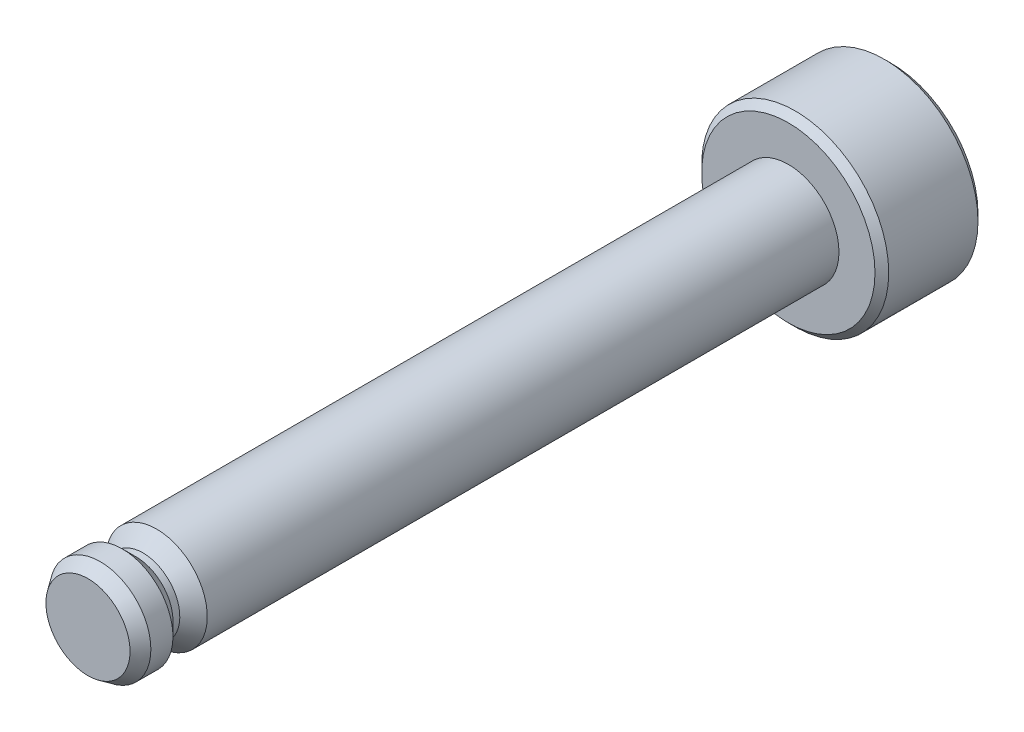
SolidWorks part; units mm, degrees
ref_plane "Front" through (0, 0, 0) normal (0, 0, 1) x (1, 0, 0)
ref_plane "Top" through (0, 0, 0) normal (0, 1, 0) x (1, 0, 0)
ref_plane "Right" through (0, 0, 0) normal (1, 0, 0) x (0, 0, -1)
sketch "Sketch2" plane through (0, 0, 0) normal (0, 0, 1) x (1, 0, 0)
  circle A0 centre (0, 0) radius 1.475
  dimension "D1" = 2.95
extrude "Shaft" add sketch "Sketch2" along normal blind 20.4
sketch "Sketch5" plane through (0, 0, 0) normal (0, 0, 1) x (1, 0, 0)
  circle A0 centre (0, 0) radius 2.725
  dimension "D1" = 5.45
extrude "Head" add sketch "Sketch5" against normal blind 3
chamfer "Chamfer1" distance 0.25 angle 55 1 edges at (1.475, 0, 20.4) first distance on face at (1.475, 0, 20.4)
chamfer "Deburs" distance 0.2 angle 45 2 edges at (2.725, 0, 0) (2.725, 0, -3)
sketch "Sketch6" plane through (0, 0, 0) normal (1, 0, 0) x (0, 0, -1)
  line L0 (0, 0) -> (-18.9, 0) construction
  line L1 (-18.9, 0) -> (-18.9, 1.075) construction
  line L2 (0, 1.475) -> (-20.043, 1.475) construction
  line L3 (-19.4, 1.475) -> (-18.4, 1.475)
  line L4 (-18.4, 1.475) -> (-18.8, 1.075)
  line L5 (-18.8, 1.075) -> (-19, 1.075)
  line L6 (-19, 1.075) -> (-19.4, 1.475)
  line L7 (-18.9, 1.075) -> (-18.9, 1.475) construction
  dimension "D1" = 18.9
  dimension "D2" = 0.4
  dimension "D3" = 1
revolve "e-Clip Notch Long" cut sketch "Sketch6" angle 360 about L0
equation "\"D1@Sketch2\"=\"Plastic Hardware OD@Box Assy.Assembly\""
equation "\"D1@Sketch5\"=\"Countersink Diameter@Box Assy.Assembly\"-.3mm"
equation "\"D1@Head\"=\"Countersink Depth@Box Assy.Assembly\""
equation "\"Length\"= 20mm"
equation "\"D1@Shaft\"=\"Length\"+.4mm"
equation "\"D1@Sketch6\"=\"Length\"-1.1mm"
